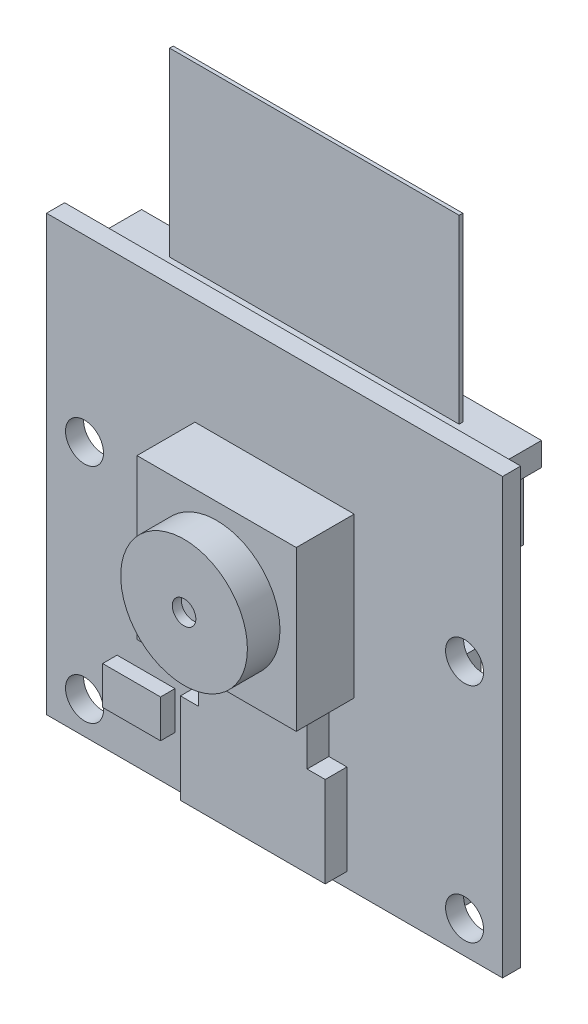
SolidWorks part; units mm, degrees
ref_plane "Přední rovina" through (0, 0, 0) normal (0, 0, 1) x (1, 0, 0)
ref_plane "Horní rovina" through (0, 0, 0) normal (0, 1, 0) x (1, 0, 0)
ref_plane "Pravá rovina" through (0, 0, 0) normal (1, 0, 0) x (0, 0, -1)
sketch "Skica1" plane through (0, 0, 0) normal (0, 0, 1) x (1, 0, 0)
  line L0 (0, -4.05) -> (0, 0) construction
  line L6 (-4.4, -2.7) -> (4.4, -2.7)
  line L7 (-21.3919, 19.9602) -> (21.3919, 19.9602)
  line L8 (-21.3919, 19.9602) -> (-21.3919, -19.9602)
  line L9 (-21.3919, -19.9602) -> (21.3919, -19.9602)
  line L10 (21.3919, 19.9602) -> (21.3919, -19.9602)
  line L11 (-21.3919, 19.9602) -> (21.3919, -19.9602) construction
  line L12 (-21.3919, -19.9602) -> (21.3919, 19.9602) construction
  line L13 (10.5, -10.2) -> (-10.5, -10.2) construction
  line L14 (10.5, -10.2) -> (10.5, 2.1) construction
  line L15 (10.5, 2.1) -> (-10.5, 2.1) construction
  line L16 (-10.5, -10.2) -> (-10.5, 2.1) construction
  line L17 (10.5, -10.2) -> (-10.5, 2.1) construction
  line L18 (10.5, 2.1) -> (-10.5, -10.2) construction
  line L19 (0, -4.05) -> (46.9713, -4.05) construction
  line L20 (-4.4, -2.7) -> (-4.4, 6.1)
  line L21 (12.6, -12) -> (-12.6, -12)
  line L22 (12.6, -12) -> (12.6, 12)
  line L23 (12.6, 12) -> (-12.6, 12)
  line L24 (-12.6, -12) -> (-12.6, 12)
  line L25 (12.6, -12) -> (-12.6, 12) construction
  line L26 (12.6, 12) -> (-12.6, -12) construction
  line L27 (-4.4, 6.1) -> (4.4, 6.1)
  line L28 (4.4, -2.7) -> (4.4, 6.1)
  line L29 (-4.4, -2.7) -> (4.4, 6.1) construction
  line L30 (-4.4, 6.1) -> (4.4, -2.7) construction
  circle A0 centre (-10.5, 2.1) radius 1.05
  circle A1 centre (10.5, 2.1) radius 1.05
  circle A2 centre (10.5, -10.2) radius 1.05
  circle A3 centre (-10.5, -10.2) radius 1.05
  circle A4 centre (0, 1.7) radius 3.5
  point P0 (41.1239, 15.3264)
  point P1 (0, 1.7)
  point P5 (0, 12)
  point P6 (0, 0)
  point P44 (0, 0)
  dimension "D5" = 2.1
  dimension "D6" = 0.75
  dimension "D8" = 7
  dimension "D1" = 25.2
  dimension "D2" = 24
  dimension "D3" = 12.3
  dimension "D4" = 21
  dimension "D7" = 8.8
  dimension "D9" = 5.9
extrude "Přidat vysunutím1" add sketch "Skica1" against normal blind 1 contours L24 L21 L22 L23 A1 A0 L28 L6 L20 L27 A2 A3 | L6 L28 L27 L20 A4 | A4 region at (-4.2755, 1.7, 0) region at (0, -11.652, 0) region at (0, 1.7, 0)
extrude "Přidat vysunutím2" add sketch "Skica1<3>" along normal blind 3.2 contours L6 L28 L27 L20 A4 region at (-4.2755, 1.7, 0)
sketch "Skica1<3>" plane through (0, 0, 0) normal (0, 0, 1) x (1, 0, 0) same geometry as "Skica1"
extrude "Přidat vysunutím3" add sketch "Skica1<4>" along normal blind 5 contours A4 region at (0, 1.7, 0)
sketch "Skica1<4>" plane through (0, 0, 0) normal (0, 0, 1) x (1, 0, 0) same geometry as "Skica1"
sketch "Skica2" plane through (0, 0, 0) normal (0, 0, 1) x (1, 0, 0)
  line L0 (-4.4, -2.7) -> (4.4, -2.7) construction
  line L1 (-4, -11.2) -> (4, -11.2)
  line L2 (-4, -11.2) -> (-4, -6.2)
  line L3 (-4, -6.2) -> (4, -6.2)
  line L4 (4, -11.2) -> (4, -6.2)
  line L5 (-4, -11.2) -> (4, -6.2) construction
  line L6 (-4, -6.2) -> (4, -11.2) construction
  line L7 (-3, -6.2) -> (3, -6.2)
  line L8 (-3, -6.2) -> (-3, -2.7)
  line L9 (-3, -2.7) -> (3, -2.7)
  line L10 (3, -6.2) -> (3, -2.7)
  line L11 (-3, -6.2) -> (3, -2.7) construction
  line L12 (-3, -2.7) -> (3, -6.2) construction
  line L13 (-4.4, -2.7) -> (4.4, -2.7) construction
  point P0 (0, -8.7)
  point P5 (0, -4.45)
  line M18 (4.4, -2.7) -> (-4.4, -2.7)
  dimension "D1" = 8
  dimension "D2" = 5
  dimension "D3" = 8.5
  dimension "D4" = 6
extrude "Přidat vysunutím4" add sketch "Skica2" along normal blind 1.2 contours L1 L4 L3 L2 | L3 L10 L8 M18 region at (0, -8.7, 0) region at (0, -4.45, 0)
sketch "Skica3" plane through (0, 0, -1) normal (0, 0, -1) x (-1, 0, 0)
  line L0 (-12.6, 12) -> (12.6, 12) construction
  line L1 (-10.05, 5.6) -> (10.05, 5.6)
  line L2 (-10.05, 5.6) -> (-10.05, 9.8)
  line L3 (-10.05, 9.8) -> (10.05, 9.8)
  line L4 (10.05, 5.6) -> (10.05, 9.8)
  line L5 (-10.05, 5.6) -> (10.05, 9.8) construction
  line L6 (-10.05, 9.8) -> (10.05, 5.6) construction
  line L7 (-11.05, 9.8) -> (11.05, 9.8)
  line L8 (-11.05, 9.8) -> (-11.05, 11.1)
  line L9 (-11.05, 11.1) -> (11.05, 11.1)
  line L10 (11.05, 9.8) -> (11.05, 11.1)
  line L11 (-11.05, 9.8) -> (11.05, 11.1) construction
  line L12 (-11.05, 11.1) -> (11.05, 9.8) construction
  point P0 (0, 7.7)
  point P5 (0, 10.45)
  dimension "D1" = 22.1
  dimension "D2" = 20.1
  dimension "D3" = 4.2
  dimension "D4" = 1.3
  dimension "D5" = 0.9
extrude "Přidat vysunutím5" add sketch "Skica3" along normal blind 2.7 contours L1 L4 L3 L2 | L7 L10 L9 L8 L3 region at (0, 7.7, -1) region at (0, 10.45, -1)
sketch "Skica4" plane through (0, 0, -1) normal (0, 0, -1) x (-1, 0, 0)
  line L0 (-12.6, -12) -> (12.6, -12) construction
  line L1 (8.8, -11) -> (-9.1, -11)
  line L2 (8.8, -11) -> (8.8, 1)
  line L3 (8.8, 1) -> (-9.1, 1)
  line L4 (-9.1, -11) -> (-9.1, 1)
  line L5 (8.8, -11) -> (-9.1, 1) construction
  line L6 (8.8, 1) -> (-9.1, -11) construction
  line L7 (12.6, -12) -> (12.6, 12) construction
  line L8 (-12.6, -12) -> (-12.6, 12) construction
  point P0 (-0.15, -5)
  dimension "D1" = 1
  dimension "D2" = 3.8
  dimension "D3" = 3.5
  dimension "D4" = 13
extrude "Přidat vysunutím6" add sketch "Skica4" along normal blind 1.3
sketch "Skica5" plane through (0, 0, 0) normal (0, 0, 1) x (1, 0, 0)
  line L0 (-12.6, -12) -> (-12.6, 12) construction
  line L1 (-8.7, -9.3) -> (-5.5, -9.3)
  line L2 (-8.7, -9.3) -> (-8.7, -7.2)
  line L3 (-8.7, -7.2) -> (-5.5, -7.2)
  line L4 (-5.5, -9.3) -> (-5.5, -7.2)
  line L5 (-8.7, -9.3) -> (-5.5, -7.2) construction
  line L6 (-8.7, -7.2) -> (-5.5, -9.3) construction
  line L7 (12.6, -12) -> (-12.6, -12) construction
  point P0 (-7.1, -8.25)
  dimension "D1" = 2.1
  dimension "D2" = 3.2
  dimension "D3" = 3.9
  dimension "D4" = 2.7
extrude "Přidat vysunutím7" add sketch "Skica5" along normal blind 0.8
sketch "Skica6" plane through (0, 0, 5) normal (0, 0, 1) x (1, 0, 0)
  circle A0 centre (0, 1.7) radius 0.65
  dimension "D1" = 1.3
extrude "Odebrat vysunutím1" cut sketch "Skica6" against normal blind 0.5
sketch "Skica7" plane through (0, 11.1, 0) normal (0, 1, 0) x (1, 0, 0)
  line L0 (11.05, 3.7) -> (-11.05, 3.7) construction
  line L1 (8, 2.4) -> (-8, 2.4)
  line L2 (8, 2.4) -> (8, 2.2)
  line L3 (8, 2.2) -> (-8, 2.2)
  line L4 (-8, 2.4) -> (-8, 2.2)
  line L5 (8, 2.4) -> (-8, 2.2) construction
  line L6 (8, 2.2) -> (-8, 2.4) construction
  point P0 (0, 2.3)
  dimension "D1" = 16
  dimension "D2" = 0.2
  dimension "D3" = 1.3
extrude "Přidat vysunutím9" add sketch "Skica7" along normal blind 10
ref_plane "Plane1" through (0, 1.7, 0) normal (0, -1, 0) x (-1, 0, 0)
